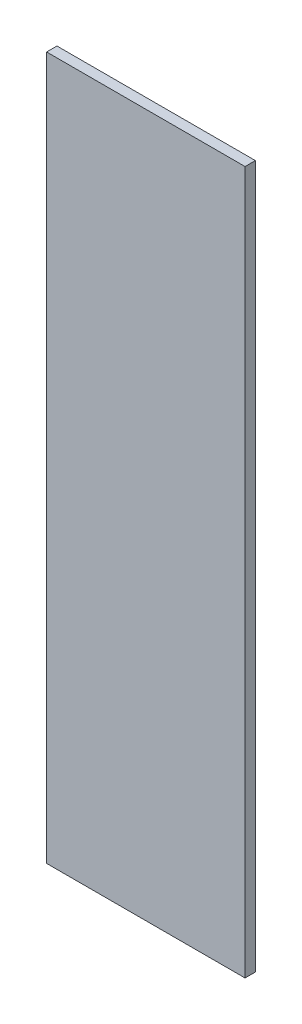
SolidWorks part; units mm, degrees
material "PC High Viscosity"
ref_plane "Front Plane" through (0, 0, 0) normal (0, 0, 1) x (1, 0, 0)
ref_plane "Top Plane" through (0, 0, 0) normal (0, 1, 0) x (1, 0, 0)
ref_plane "Right Plane" through (0, 0, 0) normal (1, 0, 0) x (0, 0, -1)
sketch "Sketch1" plane through (0, 0, 0) normal (0, 0, 1) x (1, 0, 0)
  line L1 (-48, -200) -> (48, -200)
  line L2 (-48, -200) -> (-48, 200)
  line L3 (-48, 200) -> (48, 200)
  line L4 (48, -200) -> (48, 200)
  line L5 (-48, -200) -> (48, 200) construction
  line L6 (-48, 200) -> (48, -200) construction
  point P0 (0, 0)
  dimension "D1" = 96
  dimension "D2" = 400
extrude "Boss-Extrude1" add sketch "Sketch1" along normal mid plane 5
sketch "Sketch2" plane through (0, 0, 2.5) normal (0, 0, 1) x (1, 0, 0)
  line L0 (50, 140) -> (48, 140) construction
  line L1 (-155.214, 211.8255) -> (203.9552, 211.8255)
  line L2 (-155.214, 211.8255) -> (-155.214, 140)
  line L3 (-155.214, 140) -> (203.9552, 140)
  line L4 (203.9552, 211.8255) -> (203.9552, 140)
extrude "Cut-Extrude1" cut sketch "Sketch2" against normal through all
